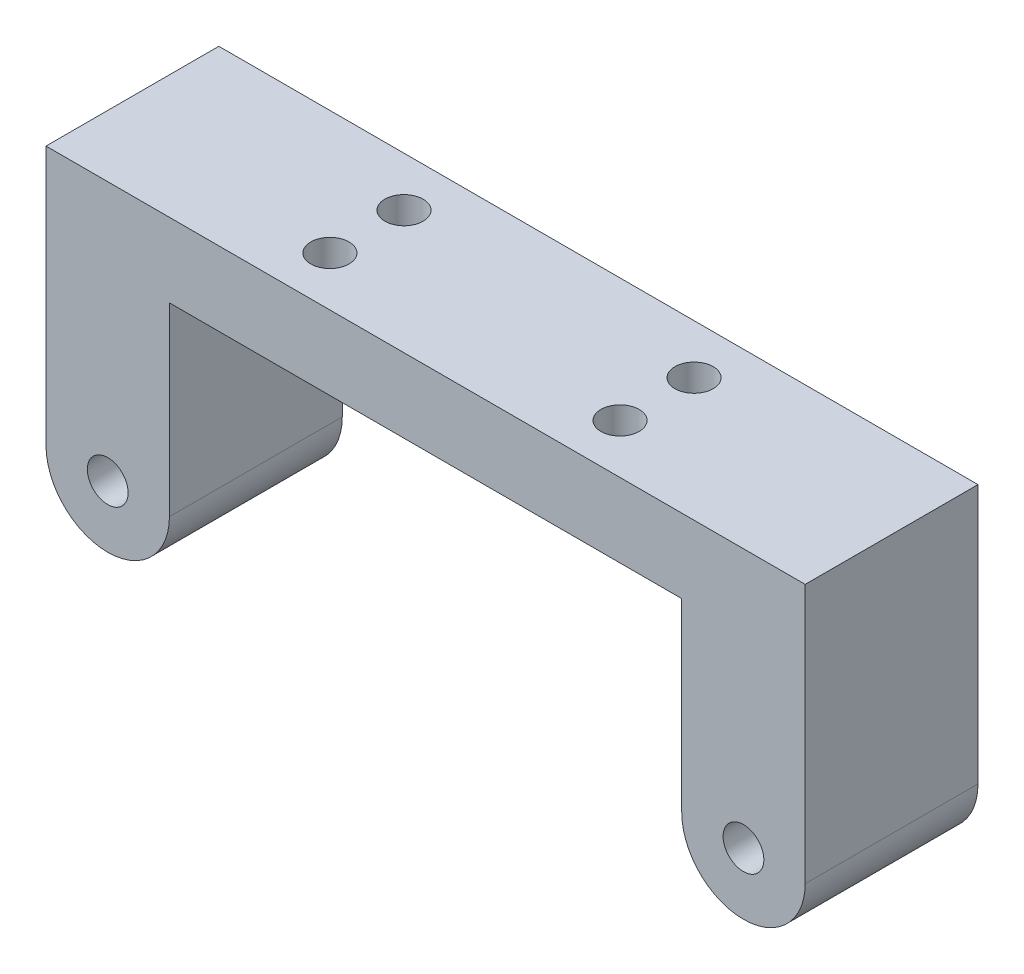
SolidWorks part; units mm, degrees
ref_plane "Front" through (0, 0, 0) normal (0, 0, 1) x (1, 0, 0)
ref_plane "Top" through (0, 0, 0) normal (0, 1, 0) x (1, 0, 0)
ref_plane "Right" through (0, 0, 0) normal (1, 0, 0) x (0, 0, -1)
sketch "Sketch1" plane through (0, 0, 0) normal (0, 1, 0) x (1, 0, 0)
  line L1 (0, 0) -> (61.5, 0)
  line L2 (0, 0) -> (0, -14)
  line L3 (0, -14) -> (61.5, -14)
  line L4 (61.5, 0) -> (61.5, -14)
  dimension "D1" = 14
  dimension "D2" = 61.5
extrude "Boss-Extrude1" add sketch "Sketch1" along normal blind 6
sketch "Sketch2" plane through (0, 6, 0) normal (0, 1, 0) x (1, 0, 0)
  line L0 (61.5, 0) -> (0, 0) construction
  line L1 (0, 0) -> (0, -14) construction
  circle A0 centre (19, -4) radius 1.55
  circle A1 centre (42.5, -4) radius 1.55
  circle A2 centre (19, -10) radius 1.55
  circle A3 centre (42.5, -10) radius 1.55
  dimension "D1" = 3.1
  dimension "D2" = 3.1
  dimension "D3" = 4
  dimension "D4" = 4
  dimension "D6" = 23.5
  dimension "D7" = 19
  dimension "D5" = 2
extrude "Cut-Extrude1" cut sketch "Sketch2" against normal through all
sketch "Sketch3" plane through (0, 0, 0) normal (0, -1, 0) x (-1, 0, 0)
  line L0 (0, 0) -> (0, -14) construction
  line L1 (0, 0) -> (-10, 0)
  line L2 (0, 0) -> (0, -14)
  line L3 (0, -14) -> (-10, -14)
  line L4 (-10, 0) -> (-10, -14)
  line L5 (0, -14) -> (-61.5, -14) construction
  line L6 (-61.5, -14) -> (-61.5, 0) construction
  line L7 (-61.5, 0) -> (-51.5, 0)
  line L8 (-61.5, 0) -> (-61.5, -14)
  line L9 (-61.5, -14) -> (-51.5, -14)
  line L10 (-51.5, 0) -> (-51.5, -14)
  dimension "D1" = 10
  dimension "D2" = 10
extrude "Boss-Extrude2" add sketch "Sketch3" along normal blind 20
sketch "Sketch4" plane through (0, 0, 0) normal (0, 0, -1) x (-1, 0, 0)
  line L0 (0, -20) -> (-10, -20) construction
  line L1 (0, 6) -> (0, -20) construction
  line L2 (-61.5, 6) -> (-61.5, -20) construction
  line L3 (-51.5, -20) -> (-61.5, -20) construction
  circle A0 centre (-5, -15) radius 1.65
  circle A1 centre (-56.5, -15) radius 1.65
  dimension "D1" = 3.3
  dimension "D2" = 3.3
  dimension "D3" = 5
  dimension "D4" = 5
  dimension "D5" = 5
  dimension "D6" = 5
extrude "Cut-Extrude2" cut sketch "Sketch4" against normal through all
fillet "Fillet1" radius 5 4 edges at (10, -20, 7) (0, -20, 7) (51.5, -20, 7) (61.5, -20, 7)
